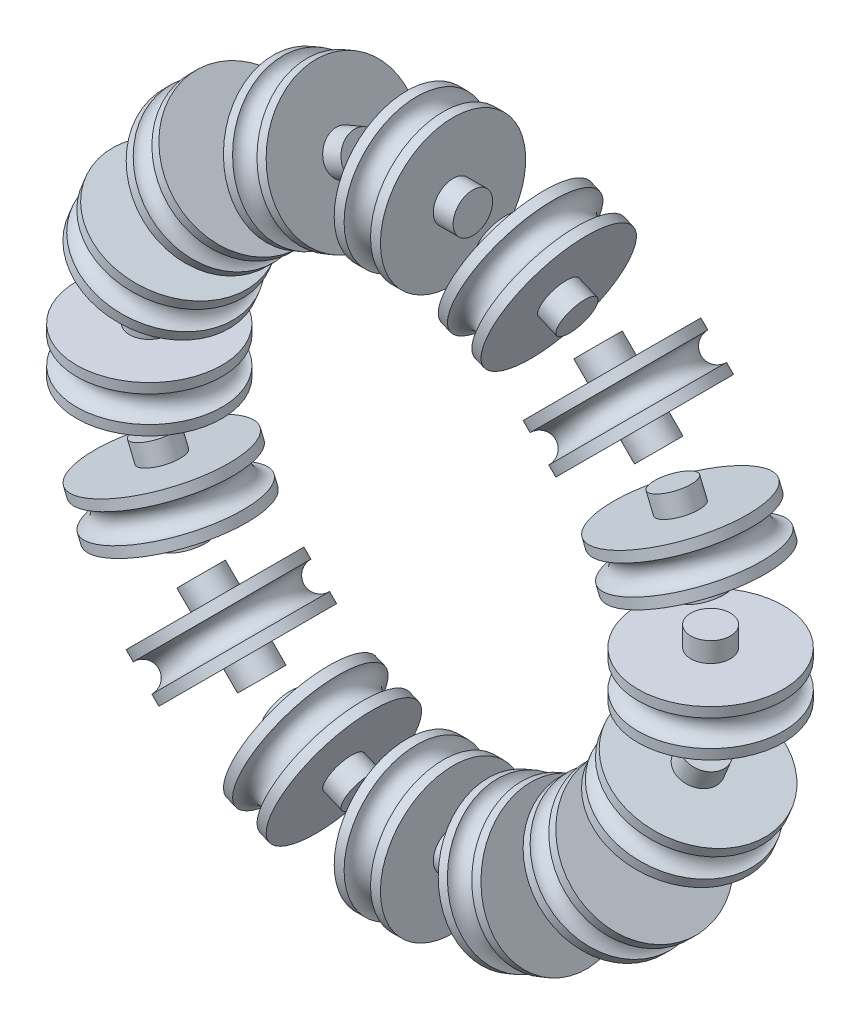
SolidWorks part; units mm, degrees
material "6061 Alloy"
ref_plane "Plano frontal" through (0, 0, 0) normal (0, 0, 1) x (1, 0, 0)
ref_plane "Plano superior" through (0, 0, 0) normal (0, 1, 0) x (1, 0, 0)
ref_plane "Plano direito" through (0, 0, 0) normal (1, 0, 0) x (0, 0, -1)
sketch "Esboço1" plane through (0, 0, 0) normal (0, 0, 1) x (1, 0, 0)
  line L1 (-1.7501, 21.25) -> (1.75, 21.25)
  line L2 (-3.25, 19.75) -> (-1.75, 19.75)
  line L3 (1.75, 15.75) -> (1.75, 19.75)
  line L4 (-3.25, 21.25) -> (-3.25, 19.75)
  line L5 (1.75, 15.75) -> (1, 15.75)
  line L6 (1.75, 21.25) -> (3.25, 21.25)
  line L7 (3.25, 21.25) -> (3.25, 19.75)
  line L8 (3.25, 19.75) -> (1.75, 19.75)
  line L9 (-1.7501, 21.25) -> (-3.25, 21.25)
  line L10 (-1.75, 15.75) -> (-1, 15.75)
  line L11 (-1.75, 15.75) -> (-1.75, 19.75)
  arc A0 (-1, 15.75) -> (1, 15.75) centre (0, 15.75) cw
revolve "Revolução1" add sketch "Esboço1" angle 360 about L1
ref_axis "Eixo1" through (0, 0, 27.4647) along (0, 0, -1)
pattern_circular "CirPattern1" count 16 over 360 about axis through (0, 0, 27.4647) along (0, 0, -1) of bodies 101
